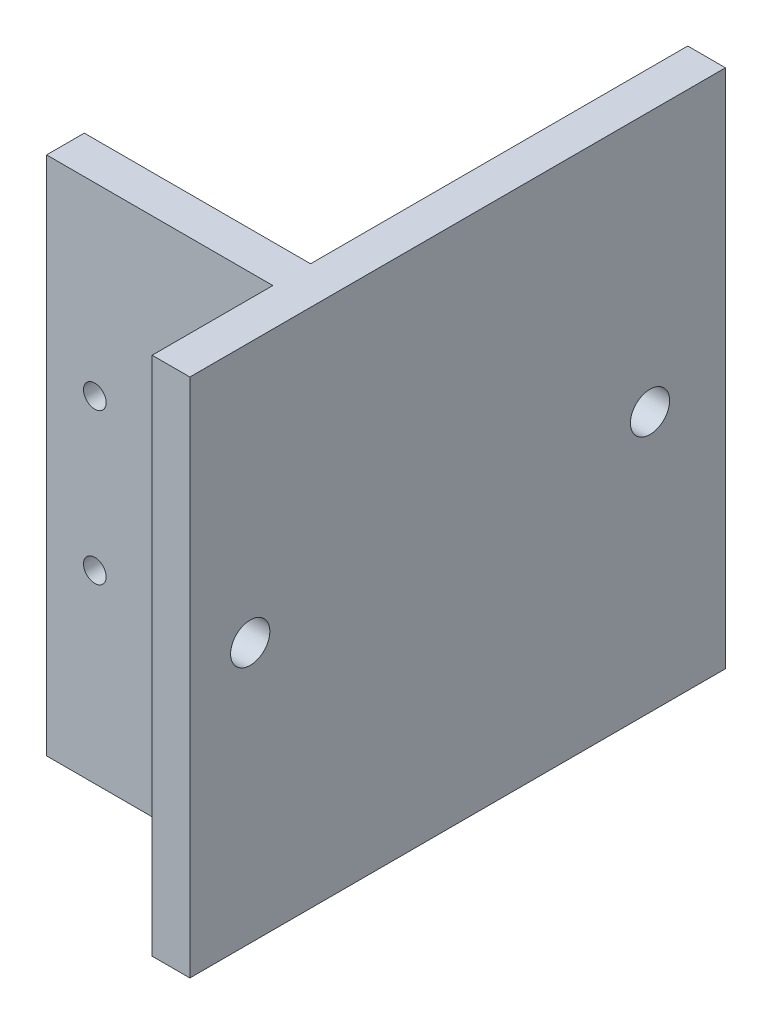
SolidWorks part; units mm, degrees
ref_plane "前视基准面" through (0, 0, 0) normal (0, 0, 1) x (1, 0, 0)
ref_plane "上视基准面" through (0, 0, 0) normal (0, 1, 0) x (1, 0, 0)
ref_plane "右视基准面" through (0, 0, 0) normal (1, 0, 0) x (0, 0, -1)
other "Configuration Table"
sketch "草图1" plane through (0, 0, 0) normal (0, 1, 0) x (1, 0, 0)
  line L0 (30, 0) -> (30, 50)
  line L1 (0, 0) -> (30, 0)
  line L2 (0, 0) -> (0, -5)
  line L3 (0, -5) -> (30, -5)
  line L5 (30, -21) -> (35, -21)
  line L6 (30, -21) -> (30, -5)
  line L7 (30, 50) -> (35, 50)
  line L8 (35, -21) -> (35, 50)
  dimension "D1" = 5
  dimension "D2" = 5
  dimension "D3" = 16
  dimension "D4" = 50
  dimension "D5" = 30
extrude "凸台-拉伸1" add sketch "草图1" along normal blind 69
hole_wizard "孔1" positions "草图2" profile "草图3" legacy end condition through all
sketch "草图2" plane through (0, 0, 5) normal (0, 0, 1) x (1, 0, 0)
  line L0 (30, 69) -> (30, 0) construction
  line L2 (0, 34.5) -> (30, 34.5) construction
  line L3 (0, 69) -> (0, 0) construction
  point P0 (26.4, 44.5)
  point P2 (26.4, 24.5)
  point P4 (6.4, 44.5)
  point P6 (6.4, 24.5)
  dimension "D1" = 3.6
  dimension "D2" = 20
  dimension "D3" = 20
  dimension "D4" = 20
sketch "草图3" plane through (26.4, 44.5, 5) normal (1, 0, 0) x (0, -1, 0)
  line L0 (0, 0) -> (0, 55)
  line L1 (0, 55) -> (1.5, 55)
  line L2 (1.5, 55) -> (1.5, 0)
  line L3 (1.5, 0) -> (0, 0)
  line L4 (0, 110) -> (0, -10) construction
  dimension "直径" = 3
  dimension "深度" = 55
sketch "草图5" plane through (30, 0, 0) normal (-1, 0, 0) x (0, 0, 1)
  line L0 (21, 34.5) -> (5, 34.5) construction
  line L1 (21, 69) -> (21, 0) construction
  line L2 (5, 69) -> (5, 0) construction
  circle A0 centre (13, 34.5) radius 2.6
  dimension "D1" = 5.2
  dimension "D2" = 8
extrude "切除-拉伸1" cut sketch "草图5" against normal blind 10
sketch "草图6" plane through (30, 0, 0) normal (-1, 0, 0) x (0, 0, 1)
  line L0 (0, 34.5) -> (-50, 34.5) construction
  line L1 (0, 69) -> (0, 0) construction
  line L2 (-50, 69) -> (-50, 0) construction
  circle A0 centre (-40, 34.5) radius 2.6
  dimension "D1" = 5.2
  dimension "D2" = 40
extrude "切除-拉伸2" cut sketch "草图6" against normal blind 10
